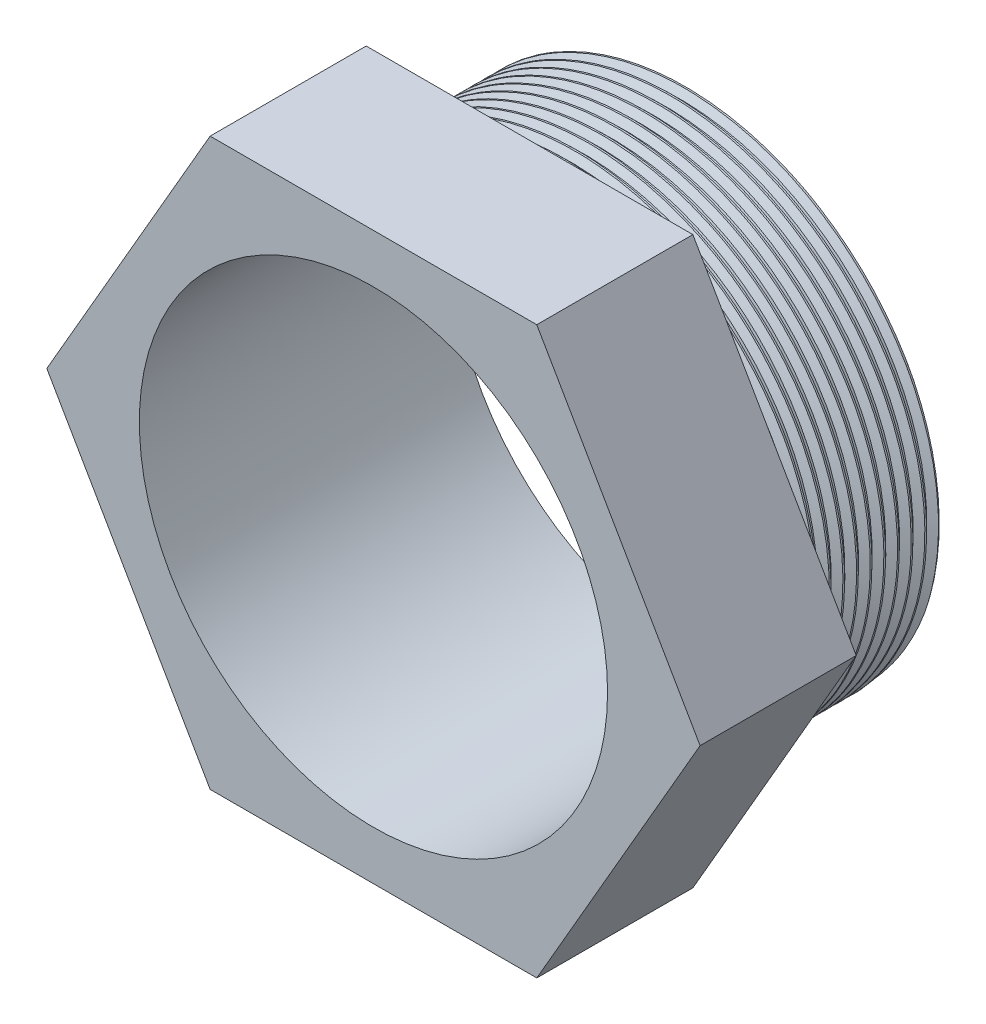
SolidWorks part; units mm, degrees
ref_plane "Front Plane" through (0, 0, 0) normal (0, 0, 1) x (1, 0, 0)
ref_plane "Top Plane" through (0, 0, 0) normal (0, 1, 0) x (1, 0, 0)
ref_plane "Right Plane" through (0, 0, 0) normal (1, 0, 0) x (0, 0, -1)
sketch "Sketch1" plane through (0, 0, 0) normal (0, 0, 1) x (1, 0, 0)
  line L1 (4.1858, -7.25) -> (8.3716, 0)
  line L2 (8.3716, 0) -> (4.1858, 7.25)
  line L3 (4.1858, 7.25) -> (-4.1858, 7.25)
  line L4 (-4.1858, 7.25) -> (-8.3716, 0)
  line L5 (-8.3716, 0) -> (-4.1858, -7.25)
  line L6 (-4.1858, -7.25) -> (4.1858, -7.25)
  circle A0 centre (0, 0) radius 6
  circle A1 centre (0, 0) radius 7.25 construction
  circle A2 centre (0, 0) radius 6.5
  point P3 (0, 7.25)
  dimension "D1" = 14.5
  dimension "D2" = 12
  dimension "D3" = 13
extrude "Boss-Extrude2" add sketch "Sketch1" along normal blind 4 contours A2 A0 | L5 L6 L1 L2 L3 L4 A2 region at (0, -7.0285, 0) region at (-6.3162, 0, 0)
extrude "Boss-Extrude3" add sketch "Sketch1<5>" against normal blind 4 contours A2 A0 region at (-6.3162, 0, 0)
sketch "Sketch1<5>" plane through (0, 0, 0) normal (0, 0, 1) x (1, 0, 0) same geometry as "Sketch1"
thread "Thread1" pitch 0.35 method cut profile "Thread Profile1" start angle 0, offset 0, length 0, pitch 0.35, diameter 13
ref_plane "Plane1" through (-6.5, 0, 0) normal (0, -1, 0) x (-1, 0, 0)
sketch "Thread Profile1" plane through (-6.5, 0, 0) normal (0, -1, 0) x (-1, 0, 0)
  line L0 (0, 0) -> (0, 0.35) construction
  line L11 (0, 0) -> (0, 0.3062)
  line L12 (0, 0.3062) -> (-0.1894, 0.1969)
  line L13 (-0.1894, 0.1969) -> (-0.1894, 0.1094)
  line L15 (-0.1894, 0.1094) -> (0, 0)
  line L17 (-0.1894, 0.1531) -> (0, 0.1531) construction
  point P2 (0, 0)
  dimension "Pitch" = 0.35
  dimension "Profile_Angle" = 60
  dimension "Profile_Land" = 0.0875
  dimension "Profile_Height" = 0.1894
